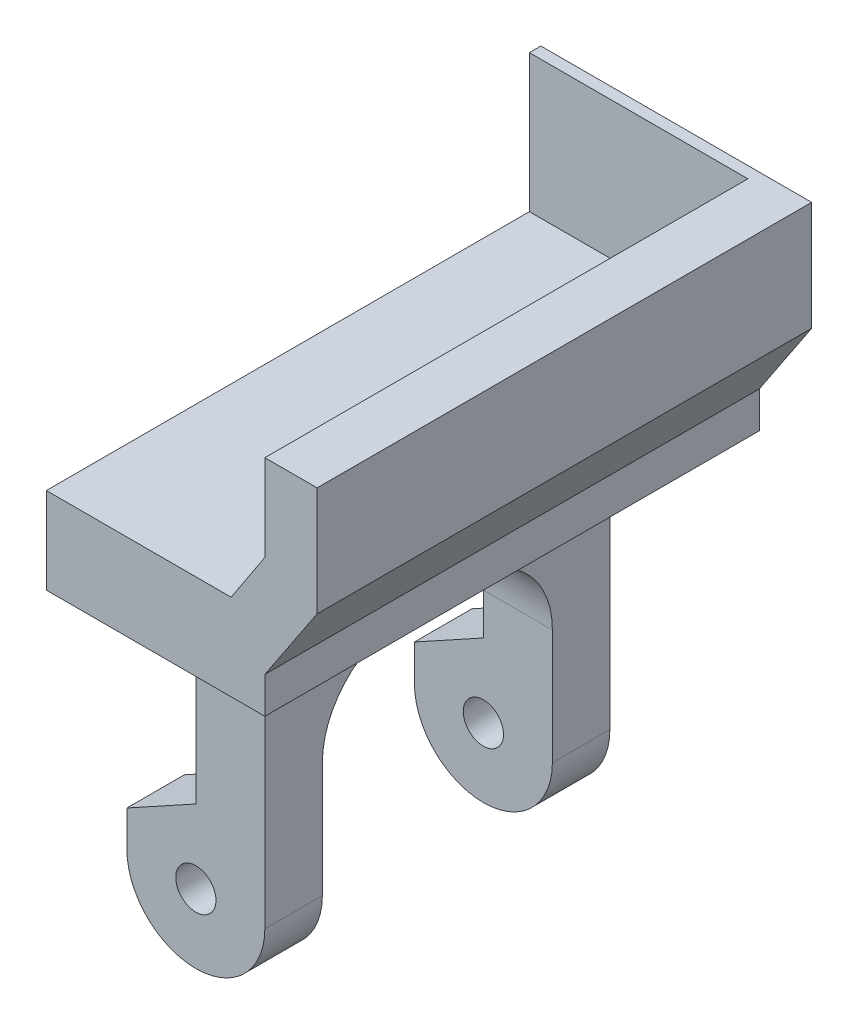
SolidWorks part; units mm, degrees
ref_plane "Front Plane" through (0, 0, 0) normal (0, 0, 1) x (1, 0, 0)
ref_plane "Top Plane" through (0, 0, 0) normal (0, 1, 0) x (1, 0, 0)
ref_plane "Right Plane" through (0, 0, 0) normal (1, 0, 0) x (0, 0, -1)
sketch "Esquisse1" plane through (0, 0, 0) normal (0, 0, 1) x (1, 0, 0)
  line L0 (-12, 0) -> (-12, 6.189)
  line L1 (-12, 6.189) -> (0, 12.796)
  line L2 (0, 12.796) -> (0, 40)
  line L3 (12, 0) -> (12, 40)
  line L4 (0, 40) -> (12, 40)
  circle A0 centre (0, 0) radius 3.5
  arc A1 (-12, 0) -> (12, 0) centre (0, 0) ccw
  point P3 (0, 12.796)
  dimension "D1" = 7
  dimension "D2" = 12
  dimension "D3" = 40
extrude "Boss.-Extru.1" add sketch "Esquisse1" along normal blind 10
sketch "Esquisse2" plane through (0, 40, 0) normal (0, 1, 0) x (1, 0, 0)
  line L0 (0, -10) -> (0, -60)
  line L1 (0, -60) -> (12, -60)
  line L2 (12, -60) -> (12, -10)
  line L4 (12, 0) -> (0, 0)
  line L5 (0, 0) -> (0, -10)
  line L6 (0, -10) -> (12, -10)
  line L7 (12, -10) -> (12, 0)
  line L8 (12, 0) -> (0, 0)
  line L9 (0, 0) -> (0, -10)
  line L11 (12, -10) -> (12, 0)
  dimension "D2" = 50
  dimension "D1" = 0
extrude "Boss.-Extru.2" add sketch "Esquisse2" along normal blind 5 separate body
ref_plane "Plan1" through (0, 0, 30) normal (0, 0, 1) x (1, 0, 0)
mirror "Symétrie2" about plane through (0, 0, 30) normal (0, 0, 1) of bodies 101
combine bodies "Combiner1" operation type add bodies to combine 103 102 101
sketch "Esquisse3" plane through (0, 40, 0) normal (0, -1, 0) x (1, 0, 0)
  line L4 (12, 10) -> (12, 50)
  line L5 (12, 50) -> (0, 50)
  line L6 (0, 50) -> (0, 10)
  line L7 (0, 10) -> (12, 10)
  line L8 (12, 10) -> (12, 50)
  line L9 (12, 50) -> (0, 50)
  line L10 (0, 50) -> (0, 10)
  line L11 (0, 10) -> (12, 10)
  dimension "D1" = 0
extrude "Boss.-Extru.3" add sketch "Esquisse3" along normal blind 5
fillet "Congé1" radius 15 2 edges at (6, 35, 10) (6, 35, 50)
sketch "Esquisse4" plane through (0, 45, 0) normal (0, 1, 0) x (1, 0, 0)
  line L8 (25, -73) -> (25, 13)
  line L9 (25, 13) -> (-13, 13)
  line L10 (-13, 13) -> (-13, -73)
  line L11 (-13, -73) -> (25, -73)
  line L12 (25, -73) -> (25, 13)
  line L13 (25, 13) -> (-13, 13)
  line L14 (-13, 13) -> (-13, -73)
  line L15 (-13, -73) -> (25, -73)
  dimension "D1" = 13
extrude "Boss.-Extru.4" add sketch "Esquisse4" along normal blind 15
ref_plane "Plan2" through (0, 0, 30) normal (0, 0, 1) x (1, 0, 0)
sketch "Esquisse5" plane through (0, 0, 73) normal (0, 0, 1) x (1, 0, 0)
  line L0 (25, 51.3122) -> (34.089, 64.9669)
  line L1 (25, 60) -> (25, 45) construction
  line L2 (34.089, 64.9669) -> (34.089, 83.947)
  line L3 (34.089, 83.947) -> (25, 83.947)
  line L4 (25, 83.947) -> (25, 68.9268)
  line L5 (25, 68.9268) -> (19.137, 60)
  line L6 (-13, 60) -> (25, 60) construction
  line L7 (19.137, 60) -> (25, 51.3122)
  point P10 (25, 51.3122)
  point P11 (25, 73.0232)
  point P12 (35.1814, 71.7943)
  point P13 (25, 68.9268)
  point P14 (34.089, 64.9669)
extrude "Boss.-Extru.5" add sketch "Esquisse5" against normal blind 85
sketch "Esquisse6" plane through (0, 0, -13) normal (0, 0, -1) x (-1, 0, 0)
  line L0 (-34.089, 64.9669) -> (-25, 51.3122) construction
  line L5 (-25, 83.947) -> (-34.089, 83.947) construction
  line L6 (-34.089, 83.947) -> (-34.089, 64.9669) construction
  line L7 (-25, 45) -> (13, 45) construction
  line L8 (13, 45) -> (13, 60) construction
  line L10 (-25, 60) -> (-25, 45) construction
  line L11 (-34.089, 64.9669) -> (-25, 51.3122)
  line L16 (-25, 83.947) -> (-34.089, 83.947)
  line L17 (-34.089, 83.947) -> (-34.089, 64.9669)
  line L18 (-25, 45) -> (13, 45)
  line L19 (13, 45) -> (13, 60)
  line L21 (-25, 51.3122) -> (-25, 45)
  line L22 (-25, 83.947) -> (13, 83.947)
  line L23 (13, 83.947) -> (13, 60)
extrude "Boss.-Extru.6" add sketch "Esquisse6" against normal blind 2
